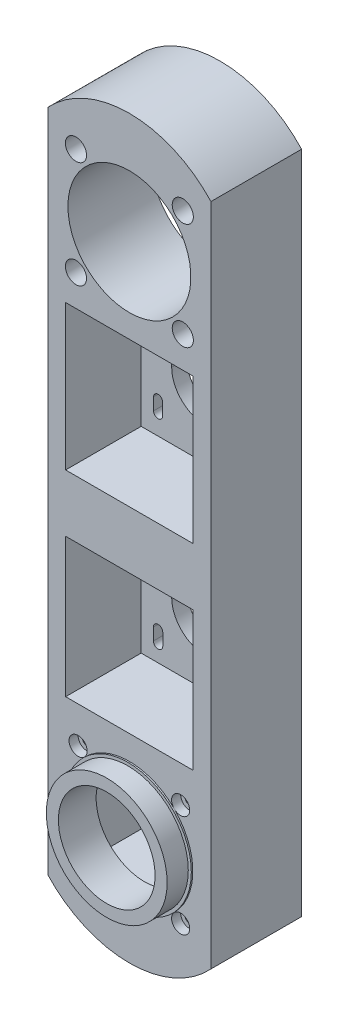
SolidWorks part; units mm, degrees
ref_plane "前视基准面" through (0, 0, 0) normal (0, 0, 1) x (1, 0, 0)
ref_plane "上视基准面" through (0, 0, 0) normal (0, 1, 0) x (1, 0, 0)
ref_plane "右视基准面" through (0, 0, 0) normal (1, 0, 0) x (0, 0, -1)
sketch "草图1" plane through (0, 0, 0) normal (0, 0, 1) x (1, 0, 0)
  line L1 (-27, 110) -> (27, 110)
  line L2 (-27, 110) -> (-27, -110)
  line L3 (-27, -110) -> (27, -110)
  line L4 (27, 110) -> (27, -110)
  line L5 (0, -110) -> (0, 110) construction
  line L6 (-27, 0) -> (27, 0) construction
  point P0 (0, 0)
  dimension "D1" = 220
  dimension "D2" = 54
extrude "凸台-拉伸1" add sketch "草图1" along normal blind 30
sketch "草图2" plane through (0, 0, 30) normal (0, 0, 1) x (1, 0, 0)
  line L0 (0, 99) -> (0, -113.7312) construction
  line L1 (-21.1, 57) -> (21.1, 57)
  line L2 (-21.1, 57) -> (-21.1, 9)
  line L3 (-21.1, 9) -> (21.1, 9)
  line L4 (21.1, 57) -> (21.1, 9)
  line L5 (0, 9) -> (0, 57) construction
  line L6 (-21.1, 33) -> (21.1, 33) construction
  line L7 (27, 110) -> (-27, 110) construction
  line L12 (0, 53) -> (0, 95) construction
  line L13 (-21, 85) -> (21, 85) construction
  point P0 (0, 33)
  point P6 (0, 85)
  dimension "D1" = 48
  dimension "D2" = 42.2
  dimension "D3" = 25
  dimension "D4" = 52
extrude "切除-拉伸1" cut sketch "草图2" against normal offset from surface (25 mm away) 5 up to face at (0, 0, 0)
sketch "草图3" plane through (0, 0, 30) normal (0, 0, -1) x (-1, 0, 0)
  line L0 (0, 105.3067) -> (0, -113.1294) construction
  line L1 (-21.1, -10) -> (21.1, -10)
  line L2 (-21.1, -10) -> (-21.1, -56)
  line L3 (-21.1, -56) -> (21.1, -56)
  line L4 (21.1, -10) -> (21.1, -56)
  line L5 (0, -56) -> (0, -10) construction
  line L6 (-21.1, -33) -> (21.1, -33) construction
  line L7 (27, -110) -> (-27, -110) construction
  line L12 (0, -95) -> (0, -53) construction
  line L13 (-21, -85) -> (21, -85) construction
  point P0 (0, -33)
  point P6 (0, -85)
  dimension "D1" = 46
  dimension "D2" = 42.2
  dimension "D3" = 25
  dimension "D4" = 52
extrude "切除-拉伸2" cut sketch "草图3" along normal offset from surface (25 mm away) 5 up to face at (0, 0, 0)
sketch "草图4" plane through (0, 0, 5) normal (0, 0, 1) x (1, 0, 0)
  line L0 (0, 33) -> (40.432, 33) construction
  line L1 (0, 0) -> (0, -107.9783) construction
  line L2 (-21.1, 57) -> (21.1, 57) construction
  line L3 (-21.1, 9) -> (21.1, 57) construction
  line L4 (21.1, 57) -> (21.1, 9) construction
  line L5 (-21.1, 57) -> (21.1, 9) construction
  line L6 (0, 35) -> (0, 31) construction
  line L7 (11, 35) -> (11, 31)
  line L8 (-11, 35) -> (-11, 31)
  line L9 (-15.5, 50.5) -> (-15.5, 46.5) construction
  line L10 (-14, 50.5) -> (-14, 46.5)
  line L11 (-17, 50.5) -> (-17, 46.5)
  line L12 (0, 33) -> (0, 63.0659) construction
  line L14 (15.5, 50.5) -> (15.5, 46.5) construction
  line L15 (14, 50.5) -> (14, 46.5)
  line L16 (17, 50.5) -> (17, 46.5)
  line L17 (15.5, 15.5) -> (15.5, 19.5) construction
  line L18 (14, 15.5) -> (14, 19.5)
  line L19 (17, 15.5) -> (17, 19.5)
  line L20 (-15.5, 15.5) -> (-15.5, 19.5) construction
  line L21 (-14, 15.5) -> (-14, 19.5)
  line L22 (-17, 15.5) -> (-17, 19.5)
  arc A17 (11, 35) -> (-11, 35) centre (0, 35) ccw
  arc A18 (-11, 31) -> (11, 31) centre (0, 31) ccw
  arc A19 (-14, 50.5) -> (-17, 50.5) centre (-15.5, 50.5) ccw
  arc A20 (-17, 46.5) -> (-14, 46.5) centre (-15.5, 46.5) ccw
  arc A21 (14, 50.5) -> (17, 50.5) centre (15.5, 50.5) cw
  arc A22 (17, 46.5) -> (14, 46.5) centre (15.5, 46.5) cw
  arc A23 (14, 15.5) -> (17, 15.5) centre (15.5, 15.5) ccw
  arc A24 (17, 19.5) -> (14, 19.5) centre (15.5, 19.5) ccw
  arc A25 (-14, 15.5) -> (-17, 15.5) centre (-15.5, 15.5) cw
  arc A26 (-17, 19.5) -> (-14, 19.5) centre (-15.5, 19.5) cw
  point P12 (0, 33)
  point P15 (0, 33)
  point P22 (-15.5, 48.5)
  point P32 (15.5, 48.5)
  point P39 (15.5, 17.5)
  point P46 (-15.5, 17.5)
  dimension "D1" = 4
  dimension "D4" = 4
  dimension "D3" = 1.5
  dimension "D6" = 11
  dimension "D2" = 15.5
  dimension "D5" = 15.5
extrude "切除-拉伸3" cut sketch "草图4" against normal through all contours L21 | L11 A20 L10 A19 | L15 A22 L16 A21 | L8 A18 L7 A17 | L18 A24 L19 A23 region at (-15.5, 17.5, 5)
sketch "草图18" plane through (0, 0, 0) normal (0, 0, 1) x (1, 0, 0)
  line L1 (-21, -63.65) -> (21, -63.65)
  line L2 (-21, -63.65) -> (-21, -106.35)
  line L3 (-21, -106.35) -> (21, -106.35)
  line L4 (21, -63.65) -> (21, -106.35)
  line L5 (0, -106.35) -> (0, -63.65) construction
  line L6 (-21, -85) -> (21, -85) construction
  point P0 (0, -85)
  dimension "D1" = 42.7
  dimension "D2" = 42
sketch "草图26" plane through (0, 0, 5) normal (0, 0, 1) x (1, 0, 0)
  line L0 (-21.1, -56) -> (21.1, -10) construction
  line L1 (-21.1, -10) -> (21.1, -56) construction
  line L2 (0, -31) -> (0, -35) construction
  line L3 (21.1, -33) -> (-21.1, -33) construction
  line L4 (0, 99) -> (0, -113.7312) construction
  line L5 (11, -31) -> (11, -35)
  line L6 (-11, -31) -> (-11, -35)
  line L7 (-15.5, -15.5) -> (-15.5, -19.5) construction
  line L8 (-13.95, -15.5) -> (-13.95, -19.5)
  line L9 (-17.05, -15.5) -> (-17.05, -19.5)
  line L10 (0, -33) -> (45.7169, -33) construction
  line L11 (0, -33) -> (0, -41.2979) construction
  line L12 (-15.5, -50.5) -> (-15.5, -46.5) construction
  line L13 (-13.95, -50.5) -> (-13.95, -46.5)
  line L14 (-17.05, -50.5) -> (-17.05, -46.5)
  line L15 (15.5, -50.5) -> (15.5, -46.5) construction
  line L16 (13.95, -50.5) -> (13.95, -46.5)
  line L17 (17.05, -50.5) -> (17.05, -46.5)
  line L18 (15.5, -15.5) -> (15.5, -19.5) construction
  line L19 (13.95, -15.5) -> (13.95, -19.5)
  line L20 (17.05, -15.5) -> (17.05, -19.5)
  arc A0 (11, -31) -> (-11, -31) centre (0, -31) ccw
  arc A1 (-11, -35) -> (11, -35) centre (0, -35) ccw
  arc A2 (-13.95, -15.5) -> (-17.05, -15.5) centre (-15.5, -15.5) ccw
  arc A3 (-17.05, -19.5) -> (-13.95, -19.5) centre (-15.5, -19.5) ccw
  arc A4 (-13.95, -50.5) -> (-17.05, -50.5) centre (-15.5, -50.5) cw
  arc A5 (-17.05, -46.5) -> (-13.95, -46.5) centre (-15.5, -46.5) cw
  arc A6 (13.95, -50.5) -> (17.05, -50.5) centre (15.5, -50.5) ccw
  arc A7 (17.05, -46.5) -> (13.95, -46.5) centre (15.5, -46.5) ccw
  arc A8 (13.95, -15.5) -> (17.05, -15.5) centre (15.5, -15.5) cw
  arc A9 (17.05, -19.5) -> (13.95, -19.5) centre (15.5, -19.5) cw
  point P8 (0, -33)
  point P16 (0, -33)
  point P23 (-15.5, -17.5)
  point P34 (-15.5, -48.5)
  point P41 (15.5, -48.5)
  point P48 (15.5, -17.5)
  dimension "D2" = 11
  dimension "D4" = 1.55
  dimension "D1" = 4
  dimension "D3" = 4
  dimension "D5" = 15.5
  dimension "D6" = 15.5
extrude "切除-拉伸13" cut sketch "草图26" against normal through all
extrude "切除-拉伸9" cut sketch "草图18" along normal blind 25
sketch "草图9" plane through (0, 0, 25) normal (0, 0, 1) x (1, 0, 0)
  line L0 (21, -85) -> (-21, -85) construction
  line L3 (0, -63.65) -> (0, -106.35) construction
  line L6 (-21, -63.65) -> (21, -63.65) construction
  line L8 (21, -106.35) -> (-21, -106.35) construction
  line L9 (-21, -106.35) -> (-21, -63.65) construction
  line L10 (21, -63.65) -> (21, -106.35) construction
  circle A1 centre (0, -85) radius 16
  circle A2 centre (-16.9706, -68.0294) radius 1.55
  circle A3 centre (16.9706, -68.0294) radius 1.55
  circle A4 centre (16.9706, -101.9706) radius 1.55
  circle A5 centre (-16.9706, -101.9706) radius 1.55
  point P26 (0, -85)
  dimension "D1" = 32
  dimension "D2" = 3.1
  dimension "D3" = 24
  dimension "D5" = 4
extrude "切除-拉伸4" cut sketch "草图9" along normal through all
sketch "草图16" plane through (0, 0, 0) normal (0, 0, 1) x (1, 0, 0)
  line L1 (-21.35, 106.35) -> (21.35, 106.35)
  line L2 (-21.35, 106.35) -> (-21.35, 63.65)
  line L3 (-21.35, 63.65) -> (21.35, 63.65)
  line L4 (21.35, 106.35) -> (21.35, 63.65)
  line L5 (0, 63.65) -> (0, 106.35) construction
  line L6 (-21.35, 85) -> (21.35, 85) construction
  point P0 (0, 85)
  dimension "D1" = 42.7
  dimension "D2" = 42.7
extrude "切除-拉伸7" cut sketch "草图16" along normal blind 2.5
sketch "草图13" plane through (0, 0, 2.5) normal (0, 0, -1) x (-1, 0, 0)
  line L0 (21.35, 85) -> (-21.35, 85) construction
  line L1 (-27, 110) -> (27, 110) construction
  line L2 (0, 85) -> (0, 93.445) construction
  line L3 (21.35, 63.65) -> (21.35, 106.35) construction
  line L4 (27, 110) -> (27, -110) construction
  line L5 (-27, -110) -> (-27, 110) construction
  line L6 (-21.35, 106.35) -> (-21.35, 63.65) construction
  line L7 (0, 106.35) -> (0, 63.65) construction
  line L8 (21.35, 106.35) -> (-21.35, 106.35) construction
  line L9 (-21.35, 63.65) -> (21.35, 63.65) construction
  circle A0 centre (0, 85) radius 20.35
  circle A1 centre (-17.6777, 102.6777) radius 2.05
  circle A2 centre (17.6777, 102.6777) radius 2.05
  circle A3 centre (17.6777, 67.3223) radius 2.05
  circle A4 centre (-17.6777, 67.3223) radius 2.05
  point P25 (0, 85)
  dimension "D1" = 40.7
  dimension "D2" = 4.1
  dimension "D3" = 25
  dimension "D6" = 25
  dimension "D5" = 4
extrude "切除-拉伸6" cut sketch "草图13" against normal through all
sketch "草图15" plane through (0, 0, 0) normal (0, 0, -1) x (-1, 0, 0)
  line L0 (-27, 110) -> (27, 110) construction
  line L1 (-27, 110) -> (27, 110)
  arc A0 (-27, 110) -> (27, 110) centre (0, 85) cw
extrude "凸台-拉伸3" add sketch "草图15" against normal up to surface (30 mm away) up to face at (15.6277, 67.3223, 30)
sketch "草图17" plane through (0, 0, 0) normal (0, 0, -1) x (-1, 0, 0)
  line L0 (0, 99) -> (0, -113.7312) construction
  circle A0 centre (-24, 100) radius 2.05
  circle A1 centre (24, 100) radius 2.05
  circle A2 centre (24, 66) radius 2.05
  circle A3 centre (-24, 66) radius 2.05
  dimension "D1" = 4.1
  dimension "D2" = 10
  dimension "D3" = 24
  dimension "D4" = 2
  dimension "D5" = 2
extrude "切除-拉伸8" cut sketch "草图17" against normal blind 8
fillet "圆角1" [suppressed] radius 10
sketch "草图21" plane through (0, 0, 30) normal (0, 0, 1) x (1, 0, 0)
  circle A0 centre (-17.6777, 102.6777) radius 3.5
  circle A1 centre (17.6777, 102.6777) radius 3.5
  circle A2 centre (17.6777, 67.3223) radius 3.5
  circle A3 centre (-17.6777, 67.3223) radius 3.5
  point P12 (0, 85)
  dimension "D1" = 7
  dimension "D2" = 4
extrude "切除-拉伸11" cut sketch "草图21" against normal blind 7.5 and the other way through all
sketch "草图28" plane through (0, 0, 30) normal (0, 0, 1) x (1, 0, 0)
  line L0 (0, 99) -> (0, -113.7312) construction
  line L1 (-27, -110) -> (27, -110) construction
  line L2 (-27, -110) -> (27, -110)
  arc A0 (-27, -110) -> (27, -110) centre (0, -84.9952) ccw
  dimension "D1" = 36.8
extrude "凸台-拉伸4" add sketch "草图28" against normal up to surface (30 mm away) up to face at (21.95, 66, 0)
sketch "草图29" plane through (0, 0, 30) normal (0, 0, 1) x (1, 0, 0)
  circle A0 centre (-16.9706, -68.0294) radius 3
  circle A1 centre (16.9706, -68.0294) radius 3
  circle A2 centre (16.9706, -101.9706) radius 3
  circle A3 centre (-16.9706, -101.9706) radius 3
  point P12 (0, -85)
  dimension "D1" = 6
  dimension "D2" = 4
extrude "切除-拉伸15" cut sketch "草图29" against normal blind 3
sketch "草图30" plane through (0, 0, 0) normal (0, 0, -1) x (-1, 0, 0)
  line L0 (0, 99) -> (0, -113.7312) construction
  circle A0 centre (-24, -100) radius 2.05
  circle A1 centre (-24, -66) radius 2.05
  circle A2 centre (24, -66) radius 2.05
  circle A3 centre (24, -100) radius 2.05
  dimension "D1" = 4.1
  dimension "D2" = 10
  dimension "D3" = 24
  dimension "D4" = 2
  dimension "D5" = 2
extrude "切除-拉伸16" cut sketch "草图30" against normal blind 8
sketch "草图31" plane through (0, 0, 30) normal (0, 0, 1) x (1, 0, 0)
  circle A0 centre (0, 85) radius 16
  circle A1 centre (0, 85) radius 20
  dimension "D1" = 40
  dimension "D2" = 32
extrude "凸台-拉伸5" [suppressed] add sketch "草图31" along normal blind 7.5
sketch "草图32" plane through (0, 0, 30) normal (0, 0, 1) x (1, 0, 0)
  circle A0 centre (0, 85) radius 21
  circle A1 centre (0, 85) radius 20
  dimension "D1" = 42
  dimension "D2" = 40
extrude "凸台-拉伸6" [suppressed] add sketch "草图32" along normal blind 0.5
sketch "草图33" plane through (0, 0, 30) normal (0, 0, 1) x (1, 0, 0)
  circle A0 centre (0, -85) radius 16
  circle A1 centre (0, -85) radius 20
  dimension "D1" = 40
  dimension "D2" = 32
extrude "凸台-拉伸7" add sketch "草图33" along normal blind 7.5
sketch "草图34" plane through (0, 0, 30) normal (0, 0, 1) x (1, 0, 0)
  circle A0 centre (0, -85) radius 20
  circle A1 centre (0, -85) radius 21
  dimension "D1" = 42
  dimension "D2" = 40
extrude "凸台-拉伸8" add sketch "草图34" along normal blind 0.5
